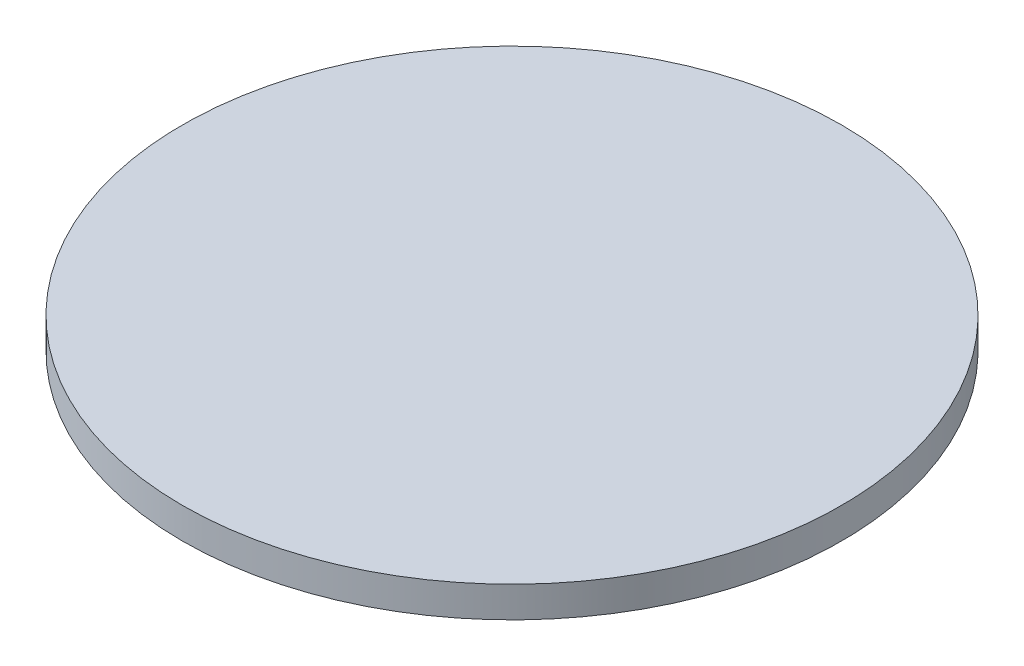
SolidWorks part; units mm, degrees
ref_plane "Front Plane" through (0, 0, 0) normal (0, 0, 1) x (1, 0, 0)
ref_plane "Top Plane" through (0, 0, 0) normal (0, 1, 0) x (1, 0, 0)
ref_plane "Right Plane" through (0, 0, 0) normal (1, 0, 0) x (0, 0, -1)
sketch "Sketch1" plane through (0, 0, 0) normal (0, 1, 0) x (1, 0, 0)
  circle A0 centre (0, 0) radius 32
extrude "Boss-Extrude1" add sketch "Sketch1" along normal blind 3
